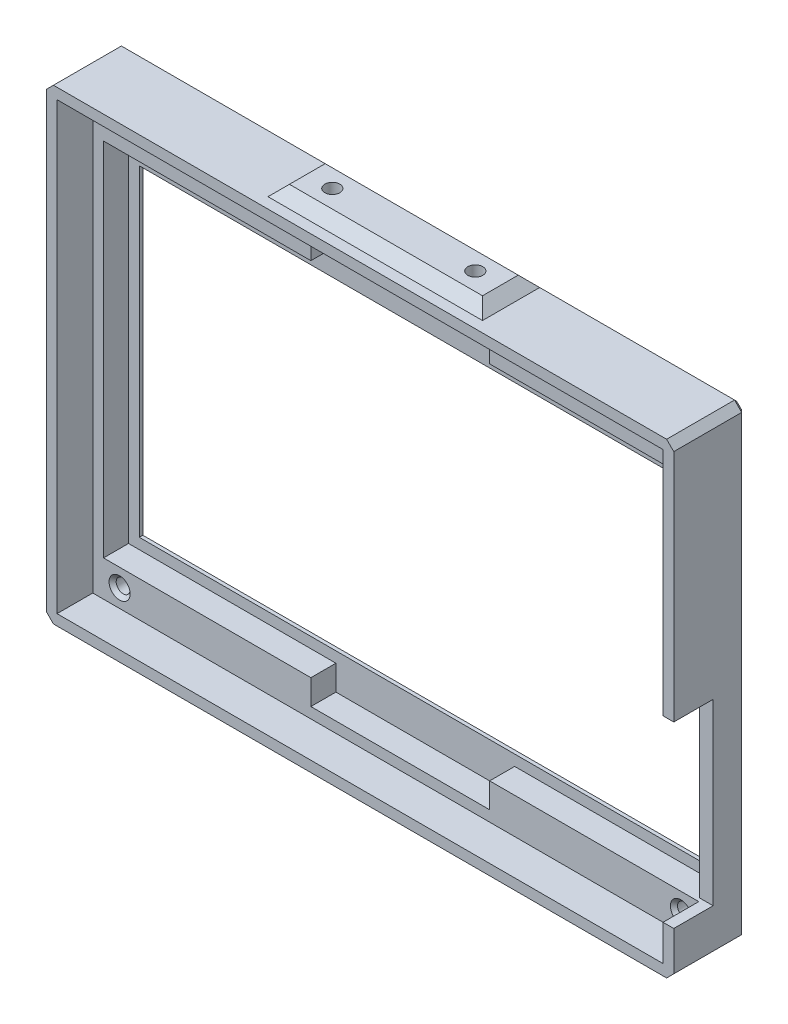
SolidWorks part; units mm, degrees
ref_plane "Alzado" through (0, 0, 0) normal (0, 0, 1) x (1, 0, 0)
ref_plane "Planta" through (0, 0, 0) normal (0, 1, 0) x (1, 0, 0)
ref_plane "Vista lateral" through (0, 0, 0) normal (1, 0, 0) x (0, 0, -1)
sketch "Croquis1" plane through (0, 0, 0) normal (0, 0, 1) x (1, 0, 0)
  line L0 (0, 0) -> (0, 30488.385) construction
  line L1 (0, 0) -> (30488.385, 0) construction
  line L3 (109, -72.5) -> (-109, -72.5)
  line L4 (109, -72.5) -> (109, 72.5)
  line L5 (109, 72.5) -> (-109, 72.5)
  line L6 (-109, -72.5) -> (-109, 72.5)
  line L7 (109, -72.5) -> (-109, 72.5) construction
  line L8 (109, 72.5) -> (-109, -72.5) construction
  line L9 (-83, 43) -> (80.5, 43) construction
  line L10 (-83, 43) -> (-83, -53) construction
  line L11 (-83, -53) -> (80.5, -53) construction
  line L12 (80.5, 43) -> (80.5, -53) construction
  line L13 (-83, 43) -> (80.5, -53) construction
  line L14 (-83, -53) -> (80.5, 43) construction
  line L15 (-80, 40) -> (77.5, 40) construction
  line L16 (-80, 40) -> (-80, -50) construction
  line L17 (-80, -50) -> (77.5, -50) construction
  line L18 (77.5, 40) -> (77.5, -50) construction
  line L19 (-80, 40) -> (77.5, -50) construction
  line L20 (-80, -50) -> (77.5, 40) construction
  circle A0 centre (-78.5, 56.5) radius 1.6 construction
  circle A1 centre (-78.5, -58) radius 1.6 construction
  circle A2 centre (78.5, -58) radius 1.6 construction
  circle A3 centre (78.5, 56.5) radius 1.6 construction
  point P7 (-1.25, -5)
  point P14 (0, 0)
  point P28 (-1.25, -5)
  dimension "D1" = 3.2
  dimension "D2" = 157
  dimension "D3" = 58
  dimension "D4" = 83
  dimension "D5" = 43
  dimension "D6" = 145
  dimension "D7" = 218
  dimension "D8" = 3
  dimension "D9" = 80.5
  dimension "D10" = 53
  dimension "D11" = 3
  dimension "D12" = 3
  dimension "D13" = 3
  dimension "D14" = 56.5
extrude "Saliente-Extruir1" add sketch "Croquis1" along normal blind 10
sketch "Croquis2" plane through (0, 0, 10) normal (0, 0, 1) x (1, 0, 0)
  line L0 (-83, 43) -> (-83, 48)
  line L1 (-83, 43) -> (80.5, 43) construction
  line L2 (-83, 43) -> (-83, -53)
  line L3 (-83, -53) -> (80.5, -53)
  line L4 (80.5, 43) -> (80.5, -53) construction
  line L5 (-83, 43) -> (80.5, -53) construction
  line L6 (-83, -53) -> (80.5, 43) construction
  line L7 (-83, 48) -> (82.7, 48)
  line L8 (82.7, 48) -> (82.7, -53)
  line L9 (82.7, -53) -> (80.5, -53)
  point P4 (-1.25, -5)
  dimension "D1" = 5
  dimension "D2" = 2.2
extrude "Cortar-Extruir1" cut sketch "Croquis2" against normal blind 7
sketch "Croquis3" plane through (0, 0, 3) normal (0, 0, 1) x (1, 0, 0)
  line L1 (-80, 40) -> (77.5, 40)
  line L2 (-80, 40) -> (-80, -50)
  line L3 (-80, -50) -> (77.5, -50)
  line L4 (77.5, 40) -> (77.5, -50)
  line L5 (-80, 40) -> (77.5, -50) construction
  line L6 (-80, -50) -> (77.5, 40) construction
  point P4 (-1.25, -5)
extrude "Cortar-Extruir2" cut sketch "Croquis3" against normal through all
chamfer "Chaflán1" distance 2 angle 45 4 edges at (-80, -5, 0) (-1.25, -50, 0) (77.5, -5, 0) (-1.25, 40, 0)
sketch "Croquis4" plane through (0, 0, 0) normal (0, 0, -1) x (-1, 0, 0)
  circle A0 centre (-78.5, 56.5) radius 1.95
  circle A1 centre (78.5, 56.5) radius 1.95
  circle A2 centre (78.5, -58) radius 1.95
  circle A3 centre (-78.5, -58) radius 1.95
  dimension "D1" = 3.9
extrude "Cortar-Extruir3" cut sketch "Croquis4" against normal through all from offset 2 offset against normal yes
sketch "Croquis5" plane through (0, 0, 10) normal (0, 0, 1) x (1, 0, 0)
  line L0 (0, 0) -> (50000, 0) construction
  line L1 (82.7, -53) -> (104.7, -53) construction
  line L2 (82.7, -53) -> (82.7, 2) construction
  line L3 (82.7, 2) -> (104.7, 2) construction
  line L4 (104.7, -53) -> (104.7, 2) construction
  line L5 (82.7, -53) -> (104.7, 2) construction
  line L6 (82.7, 2) -> (104.7, -53) construction
  line L7 (27.8965, 0) -> (-49972.1035, 0) construction
  line L8 (0, 0) -> (0, 50000) construction
  line L9 (-83, 48) -> (-83, -53) construction
  line L10 (-99, 38.2043) -> (-83, 38.2043) construction
  line L11 (-99, 38.2043) -> (-99, -38.2043) construction
  line L12 (-99, -38.2043) -> (-83, -38.2043) construction
  line L13 (-83, 38.2043) -> (-83, -38.2043) construction
  line L14 (-99, 38.2043) -> (-83, -38.2043) construction
  line L15 (-99, -38.2043) -> (-83, 38.2043) construction
  line L17 (-25, 60) -> (25, 60)
  line L18 (-25, 60) -> (-25, 48)
  line L19 (-25, 48) -> (25, 48)
  line L20 (25, 60) -> (25, 48)
  line L21 (-25, 60) -> (25, 48) construction
  line L22 (-25, 48) -> (25, 60) construction
  line L23 (-25, -48) -> (25, -60) construction
  line L24 (-25, -60) -> (25, -48) construction
  line L25 (25, -60) -> (25, -48)
  line L26 (-25, -48) -> (25, -48)
  line L27 (-25, -60) -> (-25, -48)
  line L28 (-25, -60) -> (25, -60)
  line L29 (82.7, 48) -> (-83, 48) construction
  point P4 (93.7, -25.5)
  point P13 (-91, 0)
  point P20 (0, 54)
  point P31 (0, -54)
  dimension "D1" = 22
  dimension "D2" = 55
  dimension "D3" = 16
  dimension "D4" = 50
  dimension "D5" = 12
extrude "Cortar-Extruir4" cut sketch "Croquis5" against normal up to vertex (7 mm away) up to point (77.5, -50, 3)
chamfer "Chaflán3" distance 1 angle 45 4 edges at (76.55, -58, 10) (76.55, 56.5, 10) (-80.45, 56.5, 10) (-80.45, -58, 10)
sketch "Croquis6" plane through (0, 0, 10) normal (0, 0, 1) x (1, 0, 0)
  line L1 (-89, 64.5) -> (86.5, 64.5)
  line L2 (-89, 64.5) -> (-89, -66)
  line L3 (-89, -66) -> (86.5, -66)
  line L4 (86.5, 64.5) -> (86.5, -66)
  line L5 (-89, 64.5) -> (86.5, -66) construction
  line L6 (-89, -66) -> (86.5, 64.5) construction
  point P4 (-1.25, -0.75)
  dimension "D1" = 8
  dimension "D2" = 10.5
  dimension "D3" = 8
  dimension "D4" = 8
extrude "Cortar-Extruir5" cut sketch "Croquis6" against normal through all flip side to cut
sketch "Croquis7" plane through (0, 0, 10) normal (0, 0, 1) x (1, 0, 0)
  line L1 (-89, 64.5) -> (86.5, 64.5)
  line L2 (-89, 64.5) -> (-89, -66)
  line L3 (-89, -66) -> (86.5, -66)
  line L4 (86.5, 64.5) -> (86.5, -66)
  line L5 (-89, 64.5) -> (86.5, -66) construction
  line L6 (-89, -66) -> (86.5, 64.5) construction
  line L7 (-86, 61.5) -> (83.5, 61.5)
  line L8 (-86, 61.5) -> (-86, -63)
  line L9 (-86, -63) -> (83.5, -63)
  line L10 (83.5, 61.5) -> (83.5, -63)
  line L11 (-86, 61.5) -> (83.5, -63) construction
  line L12 (-86, -63) -> (83.5, 61.5) construction
  point P4 (-1.25, -0.75)
  point P11 (-1.25, -0.75)
  dimension "D1" = 3
  dimension "D2" = 3
  dimension "D3" = 3
  dimension "D4" = 3
extrude "Saliente-Extruir2" add sketch "Croquis7" along normal blind 10
chamfer "Chaflán4" distance 2 angle 45 4 edges at (86.5, 64.5, 10) (86.5, -66, 10) (-89, -66, 10) (-89, 64.5, 10)
chamfer "Chaflán5" distance 1 angle 45 8 edges at (85.5, 63.5, 0) (86.5, -0.75, 0) (85.5, -65, 0) (-1.25, -66, 0) (-88, -65, 0) (-89, -0.75, 0) (-88, 63.5, 0) (-1.25, 64.5, 0)
sketch "Croquis8" plane through (86.5, 0, 0) normal (1, 0, 0) x (0, 0, -1)
  line L0 (0, 62.0858) -> (0, -63.5858) construction
  line L1 (-20, -3) -> (-9, -3)
  line L2 (-20, -3) -> (-20, -53)
  line L3 (-20, -53) -> (-9, -53)
  line L4 (-9, -3) -> (-9, -53)
  line L5 (-20, -3) -> (-9, -53) construction
  line L6 (-20, -53) -> (-9, -3) construction
  line L7 (-20, -64) -> (-20, 62.5) construction
  line L8 (-1, -66) -> (-20, -66) construction
  point P4 (-14.5, -28)
  point P5 (-3, -53)
  point P9 (-20, 1.3835)
  point P14 (-14.5, -53)
  dimension "D1" = 9
  dimension "D2" = 13
  dimension "D3" = 50
extrude "Cortar-Extruir6" cut sketch "Croquis8" against normal up to next
sketch "Croquis9" plane through (0, 64.5, 0) normal (0, 1, 0) x (1, 0, 0)
  line L0 (0, 0) -> (0, 50000) construction
  line L1 (84.5, -1) -> (-87, -1) construction
  line L2 (-30, -17) -> (30, -17)
  line L3 (-30, -17) -> (-30, -1)
  line L4 (-30, -1) -> (30, -1)
  line L5 (30, -17) -> (30, -1)
  line L6 (-30, -17) -> (30, -1) construction
  line L7 (-30, -1) -> (30, -17) construction
  point P3 (0, -9)
  dimension "D1" = 16
  dimension "D2" = 60
extrude "Saliente-Extruir3" add sketch "Croquis9" along normal blind 3
chamfer "Chaflán6" distance 3 angle 45 4 edges at (0, 67.5, 17) (-30, 67.5, 9) (0, 67.5, 1) (30, 67.5, 9)
sketch "Croquis10" plane through (0, 67.5, 0) normal (0, 1, 0) x (1, 0, 0)
  line L0 (0, 0) -> (0, 50000) construction
  line L1 (27, -9) -> (-49973, -9) construction
  line L2 (27, -14) -> (27, -4) construction
  circle A0 centre (20, -9) radius 2.1
  circle A1 centre (-20, -9) radius 2.1
  point P7 (27, -9)
  point P12 (0, 0)
  point P13 (0, 0)
  dimension "D1" = 4.2
  dimension "D2" = 40
extrude "Cortar-Extruir7" cut sketch "Croquis10" against normal up to next
sketch "Croquis11" plane through (0, 67.5, 0) normal (0, 1, 0) x (1, 0, 0)
  line L1 (23.9837, -9) -> (21.9919, -5.55)
  line L2 (21.9919, -5.55) -> (18.0081, -5.55)
  line L3 (18.0081, -5.55) -> (16.0163, -9)
  line L4 (16.0163, -9) -> (18.0081, -12.45)
  line L5 (18.0081, -12.45) -> (21.9919, -12.45)
  line L6 (21.9919, -12.45) -> (23.9837, -9)
  line L7 (-16.0163, -9) -> (-18.0081, -5.55)
  line L8 (-18.0081, -5.55) -> (-21.9919, -5.55)
  line L9 (-21.9919, -5.55) -> (-23.9837, -9)
  line L10 (-23.9837, -9) -> (-21.9919, -12.45)
  line L11 (-21.9919, -12.45) -> (-18.0081, -12.45)
  line L12 (-18.0081, -12.45) -> (-16.0163, -9)
  circle A0 centre (20, -9) radius 3.45 construction
  circle A1 centre (-20, -9) radius 3.45 construction
  dimension "D1" = 6.9
extrude "Cortar-Extruir8" cut sketch "Croquis11" against normal up to next from offset 3 offset against normal yes
